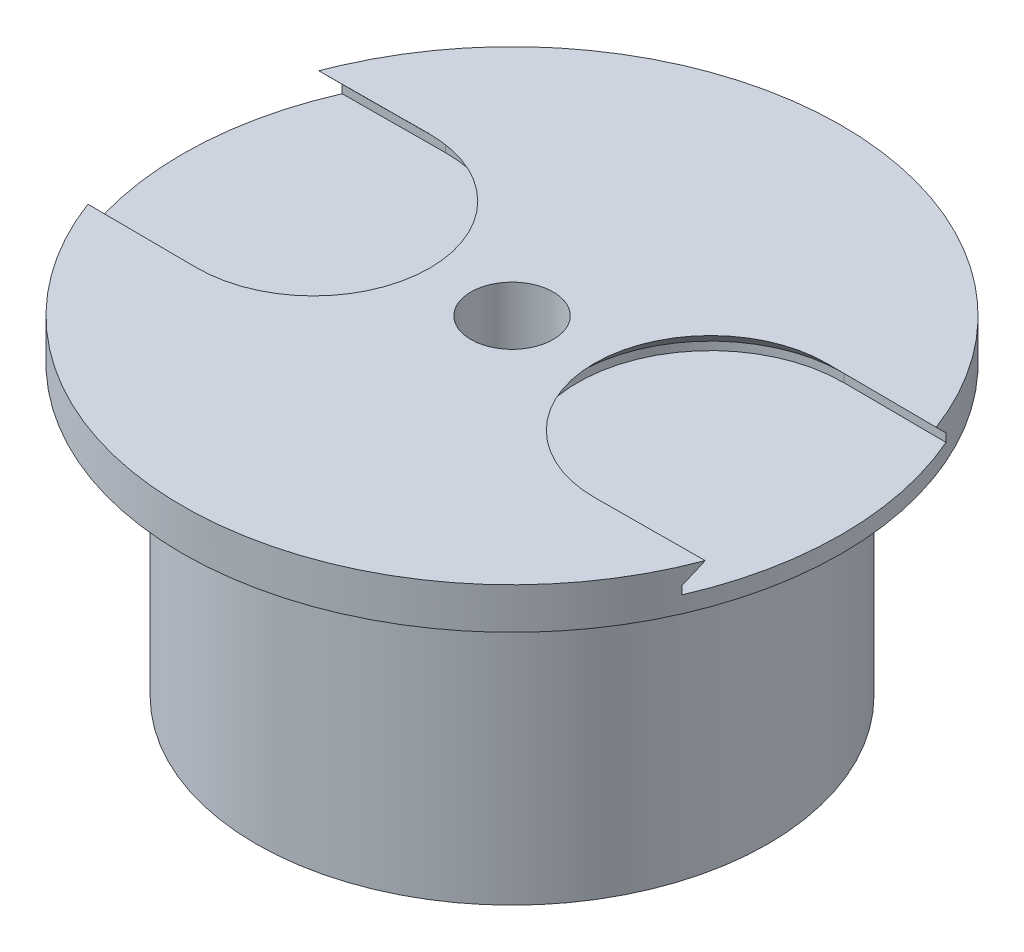
SolidWorks part; units mm, degrees
ref_plane "Front Plane" through (0, 0, 0) normal (0, 0, 1) x (1, 0, 0)
ref_plane "Top Plane" through (0, 0, 0) normal (0, 1, 0) x (1, 0, 0)
ref_plane "Right Plane" through (0, 0, 0) normal (1, 0, 0) x (0, 0, -1)
sketch "Sketch1" plane through (0, 0, 0) normal (0, 1, 0) x (1, 0, 0)
  circle A0 centre (0, 0) radius 31.06
  circle A1 centre (0, 0) radius 5
  dimension "D1" = 62.12
  dimension "D2" = 10
extrude "Boss-Extrude1" add sketch "Sketch1" along normal blind 35
sketch "Sketch18" plane through (0, 0, 0) normal (0, -1, 0) x (1, 0, 0)
  circle A0 centre (0, 0) radius 7.5
  circle A1 centre (0, 0) radius 28.66
  circle A2 centre (0, 0) radius 31.06 construction
  circle A3 centre (0, 0) radius 5 construction
  dimension "D1" = 2.4
  dimension "D2" = 2.5
extrude "Cut-Extrude12" cut sketch "Sketch18" against normal blind 13
sketch "Sketch19" plane through (0, 0, 0) normal (0, -1, 0) x (1, 0, 0)
  circle A0 centre (0, 0) radius 7.5 construction
  circle A1 centre (0, 0) radius 7.5
curve "Helix/Spiral1" pitch 12 height 12 radius 7.5 centre (0, 0, 0) axis (0, 1, 0) start towards (0, 0, -1)
sketch "Sketch20" plane through (0, 0, 0) normal (1, 0, 0) x (0, 0, -1)
  line L1 (-7.5, 0) -> (7.5, 0) construction
  line L2 (7.5, -0.6294) -> (7.5, 0.6294)
  line L4 (7.5, 0.6294) -> (8.5, 0.3457)
  line L5 (8.5, 0.3457) -> (8.5, -0.3956)
  line L6 (8.5, -0.3956) -> (7.5, -0.6294)
  line L7 (8, -0.5125) -> (8, 0.4875)
  line L8 (-7.5, 0) -> (7.5, 0)
  dimension "D1" = 1
  dimension "D2" = 29
  dimension "D3" = 1
sweep "Sweep2" add profiles "Sketch20" path "Helix/Spiral1"
pattern_circular "CirPattern8" count 4 over 360 about axis through (0, 0, 0) along (0, -1, 0) of "Sweep2"
sketch "Sketch24" plane through (0, 0, 0) normal (0, 0, 1) x (1, 0, 0)
  line L1 (-31.06, 0) -> (31.06, 0) construction
  line L2 (-31.06, 0) -> (-28.66, 0)
  line L3 (-31.06, 0) -> (-28.66, 2.4)
  line L5 (-28.66, 0) -> (-28.66, 2.4)
  line L6 (28.66, 0) -> (31.06, 0)
  dimension "D1" = 45
ref_axis "Axis1" through (0, 35, 0) along (0, -1, 0)
revolve "Cut-Revolve1" cut sketch "Sketch24" angle 360 about axis through (0, 35, 0) along (0, -1, 0)
sketch "Sketch25" plane through (0, 35, 0) normal (0, 1, 0) x (1, 0, 0)
sketch "Sketch28" plane through (0, 13, 0) normal (0, -1, 0) x (1, 0, 0)
  circle A0 centre (0, 0) radius 7.5 construction
  circle A1 centre (0, 0) radius 28.66
  circle A2 centre (0, 0) radius 28.66
  circle A3 centre (0, 0) radius 7.5
  dimension "D1" = 0
extrude "Cut-Extrude14" cut sketch "Sketch28" against normal blind 17 draft 32
sketch "Sketch30" plane through (0, 35, 0) normal (0, 1, 0) x (1, 0, 0)
  circle A0 centre (0, 0) radius 5 construction
  circle A2 centre (0, 0) radius 40
  circle A3 centre (0, 0) radius 5
  dimension "D1" = 80
extrude "Boss-Extrude2" add sketch "Sketch30" along normal blind 5
sketch "Sketch31" plane through (0, 40, 0) normal (0, 1, 0) x (1, 0, 0)
  line L0 (40, 0) -> (-40, 0)
  line L1 (40, 13.3) -> (40, -13.3)
  line L2 (40, -13.3) -> (24.1845, -13.3997)
  line L3 (40, 13.3) -> (16.7999, 13.4463)
  line L4 (0, -40) -> (0, 40)
  line L5 (-40, 13.3) -> (-16.7999, 13.4463)
  line L6 (-40, -13.3) -> (-24.1845, -13.3997)
  line L7 (-40, 13.3) -> (-40, -13.3)
  circle A0 centre (0, 0) radius 40 construction
  circle A1 centre (24.1, 0) radius 13.4
  circle A2 centre (-24.1, 0) radius 13.4
  circle M2 centre (0, 0) radius 40
  dimension "D1" = 26.8
  dimension "D2" = 26.6
  dimension "D3" = 15.9
extrude "Cut-Extrude16" cut sketch "Sketch31" against normal blind 1 from offset 2 contours A2 L0 | A2 L0 | L0 A2 L5 M2 | L6 A2 L0 M2 | A1 L0 | L0 A1 | A1 L2 L0 M2 | A1 L0 L3 M2 | A1 region at (36.0401, 40, 8.4076) region at (36.0401, 40, -8.4076) region at (24.1, 40, 5.6871) region at (24.1, 40, -5.6871) region at (-36.0401, 40, -8.4076) region at (-36.0401, 40, 8.4076) region at (-24.1, 40, 5.6871) region at (-24.1, 40, -5.6871) offset against normal yes
sketch "Sketch32" plane through (0, 40, 0) normal (0, 1, 0) x (1, 0, 0)
  line L0 (37.7191, 13.3144) -> (37.7191, -13.3144)
  line L1 (0, -40) -> (0, 40) construction
  line L2 (37.7191, 13.3144) -> (24.1845, 13.3997)
  line L3 (24.1845, -13.3997) -> (37.7191, -13.3144)
  line L4 (37.7191, 13.3144) -> (24.1845, 13.3997)
  line L5 (24.1845, -13.3997) -> (37.7191, -13.3144)
  line L6 (-24.1845, 13.3997) -> (-37.7191, 13.3144)
  line L7 (-37.7191, -13.3144) -> (-24.1845, -13.3997)
  line L8 (0, -40) -> (0, 40)
  line L9 (-24.1, -12) -> (-38.1576, -12)
  line L10 (31.06, 0) -> (24.1, 0)
  line L11 (-24.1, 12) -> (-38.1576, 12)
  line L12 (-31.06, 0) -> (-24.1, 0)
  line L13 (-24.1845, -13.3997) -> (-37.7191, -13.3144)
  line L14 (24.1, 12) -> (38.1576, 12)
  line L15 (24.1, -12) -> (38.1576, -12)
  line L16 (-37.7191, 13.3144) -> (-24.1845, 13.3997)
  line L17 (-37.7191, 13.3144) -> (-37.7191, -13.3144)
  circle A0 centre (24.1, 0) radius 12
  arc A1 (-24.1845, 13.3997) -> (-24.1845, -13.3997) centre (-24.1, 0) cw
  arc A2 (24.1845, 13.3997) -> (24.1845, -13.3997) centre (24.1, 0) ccw
  arc A3 (37.7191, -13.3144) -> (37.7191, 13.3144) centre (0, 0) ccw
  arc A4 (24.1845, 13.3997) -> (24.1845, -13.3997) centre (24.1, 0) ccw
  arc A5 (-37.7191, -13.3144) -> (37.7191, 13.3144) centre (0, 0) ccw
  arc A6 (-24.1845, -13.3997) -> (-24.1845, 13.3997) centre (-24.1, 0) ccw
  arc A7 (-37.7191, 13.3144) -> (-37.7191, -13.3144) centre (0, 0) ccw
  circle A8 centre (-24.1, 0) radius 12
  arc A9 (37.7191, 13.3144) -> (-37.7191, -13.3144) centre (0, 0) ccw
  circle M9 centre (0, 0) radius 40
  dimension "D4" = 24
  dimension "D1" = 0
  dimension "D2" = 0
extrude "Cut-Extrude17" cut sketch "Sketch32" against normal up to next contours A8 | L9 A8 L11 L17 | L17 L11 L9 M9 | A0 | A0 L15 L0 L14 | L0 L15 L14 M9 region at (38.6449, 40, 0) region at (37.4431, 40, 0) region at (32.3453, 40, -8.2453) region at (-38.6449, 40, 0) region at (-30.9095, 40, -11.7241) region at (-15.8547, 40, -8.2453)
ref_plane "Plane2" through (40, 0, 0) normal (1, 0, 0) x (0, 0, -1)
sketch "Sketch33" plane through (0, 37, 0) normal (0, 1, 0) x (1, 0, 0)
  line L0 (0, -40) -> (0, 40) construction
  line L1 (0, -40) -> (0, 40)
  line L2 (24.1845, -13.3997) -> (37.7191, -13.3144)
  line L3 (37.7191, 13.3144) -> (24.1845, 13.3997)
  line L4 (24.1845, -13.3997) -> (40, -13.3)
  line L5 (40, 13.3) -> (24.1845, 13.3997)
  line L6 (40, -40) -> (40, 40)
  line L7 (-40, -40) -> (-40, 40)
  line L8 (-40, 13.3) -> (-24.1845, 13.3997)
  line L9 (-24.1845, -13.3997) -> (-40, -13.3)
  arc A0 (-37.7191, -13.3144) -> (-37.7191, 13.3144) centre (0, 0) cw
  arc A1 (-24.1845, 13.3997) -> (-24.1845, -13.3997) centre (-24.1, 0) cw
  arc A2 (24.1845, 13.3997) -> (24.1845, -13.3997) centre (24.1, 0) ccw
  arc A3 (37.7191, -13.3144) -> (37.7191, 13.3144) centre (0, 0) ccw
  arc A4 (24.1845, 13.3997) -> (24.1845, -13.3997) centre (24.1, 0) ccw
  arc A5 (37.7191, -13.3144) -> (37.7191, 13.3144) centre (0, 0) ccw
  dimension "D1" = 0
  dimension "D2" = 40
sketch "Sketch34" plane through (40, 0, 0) normal (1, 0, 0) x (0, 0, -1)
  line L0 (-40, 37) -> (40, 37) construction
  line L1 (-40, 37) -> (40, 37)
  line L2 (-13.3997, 37) -> (-13.3, 37) construction
  line L3 (-13.3997, 37) -> (-13.3, 37)
  line L4 (-13.3, 37) -> (-16, 37)
  line L5 (-16, 37) -> (-16, 38)
  line L6 (-16, 38) -> (-13.3, 40.7)
  line L7 (-13.3, 40.7) -> (-13.3, 37)
  line L8 (-13.3144, 37) -> (-13.3144, 38) construction
  dimension "D1" = 2.7
  dimension "D2" = 45
sweep "Cut-Sweep1" cut profiles "Sketch34" path "Sketch33"
sketch "Sketch35" plane through (0, 40, 0) normal (0, 1, 0) x (1, 0, 0)
  line L4 (37.7191, 13.3144) -> (24.1845, 13.3997)
  line L5 (24.1845, -13.3997) -> (37.7191, -13.3144)
  line L6 (38.1576, -12) -> (24.1, -12)
  line L7 (24.1, 12) -> (38.1576, 12)
  line L8 (37.7191, 13.3144) -> (24.1845, 13.3997)
  line L9 (24.1845, -13.3997) -> (37.7191, -13.3144)
  line L10 (38.1576, -12) -> (24.1, -12)
  line L11 (24.1, 12) -> (38.1576, 12)
  arc A4 (24.1845, 13.3997) -> (24.1845, -13.3997) centre (24.1, 0) ccw
  arc A5 (37.7191, -13.3144) -> (38.1576, -12) centre (0, 0) ccw
  arc A6 (24.1, 12) -> (24.1, -12) centre (24.1, 0) ccw
  arc A7 (38.1576, 12) -> (37.7191, 13.3144) centre (0, 0) ccw
  arc A8 (24.1845, 13.3997) -> (24.1845, -13.3997) centre (24.1, 0) ccw
  arc A9 (37.7191, -13.3144) -> (38.1576, -12) centre (0, 0) ccw
  arc A10 (24.1, 12) -> (24.1, -12) centre (24.1, 0) ccw
  arc A11 (38.1576, 12) -> (37.7191, 13.3144) centre (0, 0) ccw
  dimension "D1" = 0
extrude "Cut-Extrude19" cut sketch "Sketch35" against normal blind 2
ref_plane "Plane3" through (-40, 0, 0) normal (-1, 0, 0) x (0, 0, 1)
sketch "Sketch37" plane through (-40, 0, 0) normal (-1, 0, 0) x (0, 0, 1)
  line L0 (40, 37) -> (-40, 37) construction
  line L1 (40, 37) -> (-40, 37)
  line L2 (-13.3, 37) -> (-13.3997, 37) construction
  line L3 (-13.3, 37) -> (-13.3997, 37)
  line L4 (-13.3, 37) -> (-16, 37)
  line L5 (-16, 37) -> (-16, 38)
  line L6 (-16, 38) -> (-13.3, 40.7)
  line L7 (-13.3, 40.7) -> (-13.3, 37)
  line L8 (-13.3144, 37) -> (-13.3144, 38) construction
  dimension "D1" = 45
  dimension "D2" = 2.7
sweep "Cut-Sweep2" cut profiles "Sketch37" path "Sketch33<3>"
sketch "Sketch33<3>" plane through (0, 37, 0) normal (0, 1, 0) x (1, 0, 0) same geometry as "Sketch33"
sketch "Sketch38" plane through (0, 40, 0) normal (0, 1, 0) x (1, 0, 0)
  line L4 (-37.7191, -13.3144) -> (-24.1845, -13.3997)
  line L5 (-24.1845, 13.3997) -> (-37.7191, 13.3144)
  line L6 (-38.1576, 12) -> (-24.1, 12)
  line L7 (-24.1, -12) -> (-38.1576, -12)
  line L8 (-37.7191, -13.3144) -> (-24.1845, -13.3997)
  line L9 (-24.1845, 13.3997) -> (-37.7191, 13.3144)
  line L10 (-38.1576, 12) -> (-24.1, 12)
  line L11 (-24.1, -12) -> (-38.1576, -12)
  arc A4 (-24.1845, -13.3997) -> (-24.1845, 13.3997) centre (-24.1, 0) ccw
  arc A5 (-37.7191, 13.3144) -> (-38.1576, 12) centre (0, 0) ccw
  arc A6 (-24.1, -12) -> (-24.1, 12) centre (-24.1, 0) ccw
  arc A7 (-38.1576, -12) -> (-37.7191, -13.3144) centre (0, 0) ccw
  arc A8 (-24.1845, -13.3997) -> (-24.1845, 13.3997) centre (-24.1, 0) ccw
  arc A9 (-37.7191, 13.3144) -> (-38.1576, 12) centre (0, 0) ccw
  arc A10 (-24.1, -12) -> (-24.1, 12) centre (-24.1, 0) ccw
  arc A11 (-38.1576, -12) -> (-37.7191, -13.3144) centre (0, 0) ccw
  dimension "D1" = 0
extrude "Cut-Extrude20" cut sketch "Sketch38" against normal blind 2
